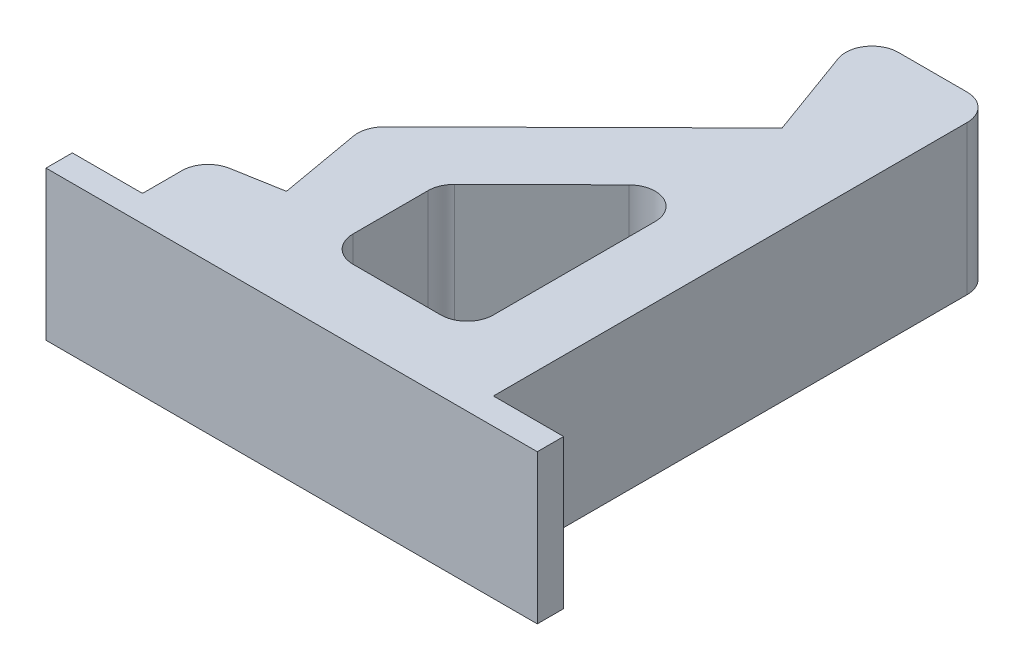
SolidWorks part; units mm, degrees
ref_plane "Front Plane" through (0, 0, 0) normal (0, 0, 1) x (1, 0, 0)
ref_plane "Top Plane" through (0, 0, 0) normal (0, 1, 0) x (1, 0, 0)
ref_plane "Right Plane" through (0, 0, 0) normal (1, 0, 0) x (0, 0, -1)
sketch "Sketch1" plane through (0, 0, 0) normal (0, 1, 0) x (1, 0, 0)
  line L0 (0, 0) -> (0, 10)
  line L1 (0, 0) -> (40, 0)
  line L2 (40, 0) -> (40, 60)
  line L3 (40, 60) -> (24.8697, 60)
  line L4 (24.8697, 60) -> (30, 45.9046)
  line L6 (30, 45.9046) -> (6.0899, 22.2435)
  line L7 (6.0899, 22.2435) -> (8, 11.4106)
  line L8 (8, 11.4106) -> (0, 10)
  line L9 (16, 8) -> (32, 8)
  line L10 (32, 8) -> (32, 36.6288)
  line L11 (32, 36.6288) -> (16, 20.7955)
  line L12 (16, 20.7955) -> (16, 8)
  point P11 (4.9388, 25.3286)
  dimension "D1" = 40
  dimension "D2" = 60
  dimension "D3" = 70
  dimension "D4" = 100
  dimension "D5" = 10
  dimension "D6" = 11
  dimension "D7" = 15
  dimension "D8" = 10
  dimension "D9" = 8
  dimension "D10" = 8
  dimension "D11" = 8
  dimension "D12" = 8
  dimension "D13" = 8
extrude "Boss-Extrude1" add sketch "Sketch1" along normal mid plane 17
fillet "Fillet1" radius 3 8 edges at (40, 0, -60) (16, 0, -8) (16, 0, -20.7955) (32, 0, -36.6288) (32, 0, -8) (0, 0, -10) (6.0899, 0, -22.2435) (24.8697, 0, -60)
sketch "Sketch2" plane through (0, 8.5, 0) normal (0, 1, 0) x (1, 0, 0)
  line L1 (0, 0) -> (-8, 0)
  line L2 (0, 0) -> (0, 3)
  line L3 (0, 3) -> (-8, 3)
  line L4 (-8, 0) -> (-8, 3)
  line L5 (40, 0) -> (48, 0)
  line L6 (40, 0) -> (40, 3)
  line L7 (40, 3) -> (48, 3)
  line L8 (48, 0) -> (48, 3)
  dimension "D1" = 3
  dimension "D2" = 8
  dimension "D3" = 8
extrude "Boss-Extrude2" add sketch "Sketch2" against normal up to surface (17 mm away) up to face at (18.7706, -8.5, -29.5137)
